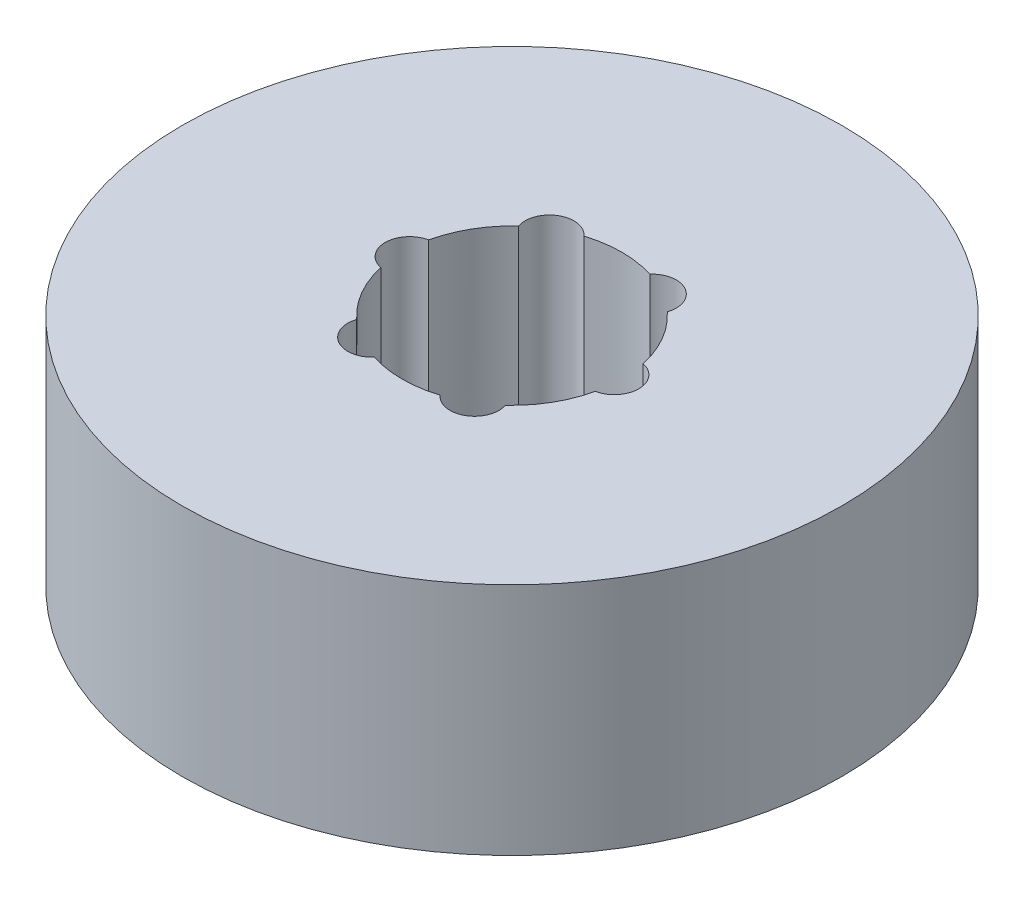
SolidWorks part; units mm, degrees
ref_plane "Front Plane" through (0, 0, 0) normal (0, 0, 1) x (1, 0, 0)
ref_plane "Top Plane" through (0, 0, 0) normal (0, 1, 0) x (1, 0, 0)
ref_plane "Right Plane" through (0, 0, 0) normal (1, 0, 0) x (0, 0, -1)
sketch "Sketch1" plane through (0, 0, 0) normal (0, 1, 0) x (1, 0, 0)
  circle A0 centre (0, 0) radius 22.5
  dimension "FLANGE_OD" = 45
extrude "Boss-Extrude1" add sketch "Sketch1" along normal blind 16
sketch "Sketch2" plane through (0, 0, 0) normal (0, 1, 0) x (1, 0, 0)
  circle A0 centre (0, 0) radius 7.5
  dimension "BORE_D" = 15
extrude "Cut-Extrude1" cut sketch "Sketch2" along normal through all
sketch "Sketch3" plane through (0, 16, 0) normal (0, 1, 0) x (1, 0, 0)
  circle A0 centre (0, 0) radius 6.985 construction
  circle A1 centre (-6.985, 0) radius 1.6676
  dimension "BOLT_D" = 3.3353
  dimension "BOLT_PCD" = 13.9699
extrude "Cut-Extrude2" cut sketch "Sketch3" against normal blind 15.7446
pattern_circular "CirPattern1" count 6 over 360 about axis through (0, 0, 0) along (0, 1, 0) of "Cut-Extrude2"
